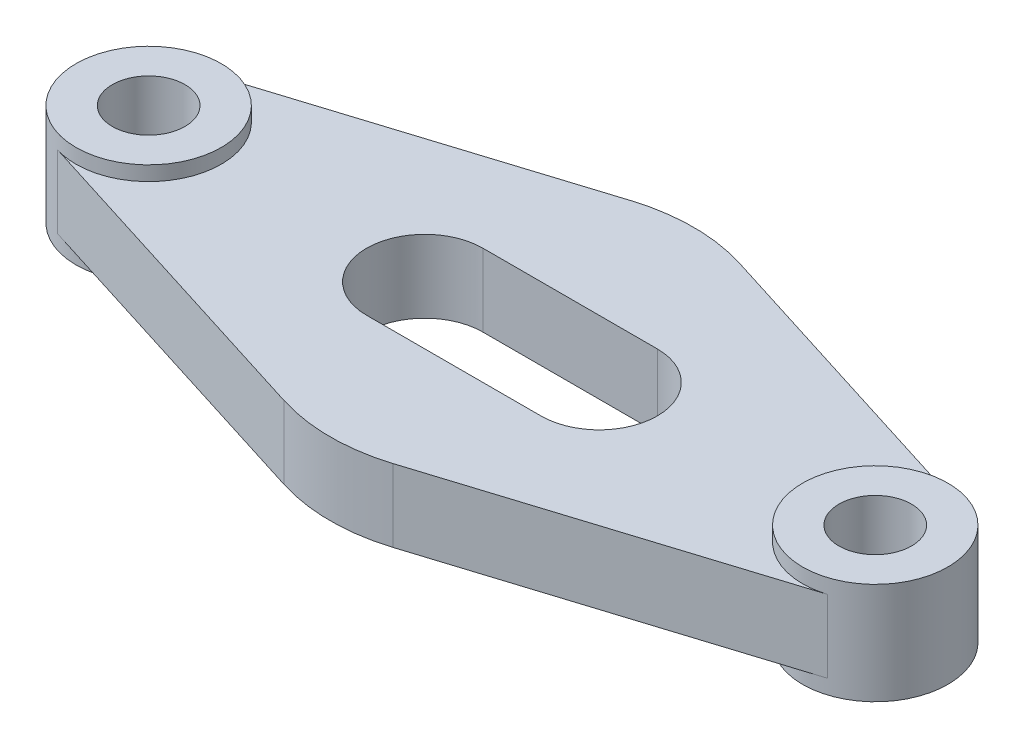
SolidWorks part; units mm, degrees
ref_plane "Alzado" through (0, 0, 0) normal (0, 0, 1) x (1, 0, 0)
ref_plane "Planta" through (0, 0, 0) normal (0, 1, 0) x (1, 0, 0)
ref_plane "Vista lateral" through (0, 0, 0) normal (1, 0, 0) x (0, 0, -1)
sketch "Croquis6" plane through (0, 0, 0) normal (0, 1, 0) x (1, 0, 0)
  line L1 (-12, -8) -> (12, -8)
  line L3 (-12, 8) -> (12, 8)
  line L4 (-53, 9.5394) -> (-7.5, 23.8485)
  line L5 (-53, -9.5394) -> (-7.5, -23.8485)
  line L6 (7.5, -23.8485) -> (53, -9.5394)
  line L7 (7.5, 23.8485) -> (53, 9.5394)
  arc A0 (12, -8) -> (12, 8) centre (12, 0) ccw
  arc A1 (-12, 8) -> (-12, -8) centre (-12, 0) ccw
  circle A4 centre (50, 0) radius 10
  circle A5 centre (-50, 0) radius 10
  arc A6 (7.5, 23.8485) -> (-7.5, 23.8485) centre (0, 0) ccw
  circle A7 centre (50, 0) radius 5
  circle A8 centre (-50, 0) radius 5
  arc A9 (-7.5, -23.8485) -> (7.5, -23.8485) centre (0, 0) ccw
  point P0 (0, 0)
  point P18 (0, 0)
  point P19 (-66.7764, -8.6965)
  point P24 (-7.7687, 23.7623)
  point P26 (0, -29.6225)
  point P27 (72.8894, -3.2845)
  point P28 (-7.8947, -28.6899)
  point P29 (3.0566, 31.9773)
  point P30 (63.0348, 9.8667)
  point P31 (-59.612, 9.1947)
  point P32 (-8.8912, 25.9258)
  point P34 (-7.5, 23.8485)
  point P35 (-7.5, 23.8485)
  point P38 (24.7232, 3.7101)
  dimension "D1" = 50
  dimension "D3" = 10
  dimension "D4" = 20
  dimension "D5" = 20
  dimension "D6" = 10
  dimension "D7" = 50
  dimension "D8" = 24
  dimension "D9" = 16
  dimension "D10" = 12
  dimension "D2" = 100
extrude "Saliente-Extruir1" add sketch "Croquis6" along normal blind 5 and the other way blind 5 contours L5 A9 L6 A4 L7 A6 L4 A5 A1 L3 A0 L1 region at (-29.8984, 0, -15.5759)
extrude "Saliente-Extruir2" add sketch "Croquis6<3>" along normal blind 7 and the other way blind 7 contours A5 A8 | A4 A7 region at (-44.2513, 0, -7.8342) region at (57.8342, 0, -5.7487)
sketch "Croquis6<3>" plane through (0, 0, 0) normal (0, 1, 0) x (1, 0, 0) same geometry as "Croquis6"
